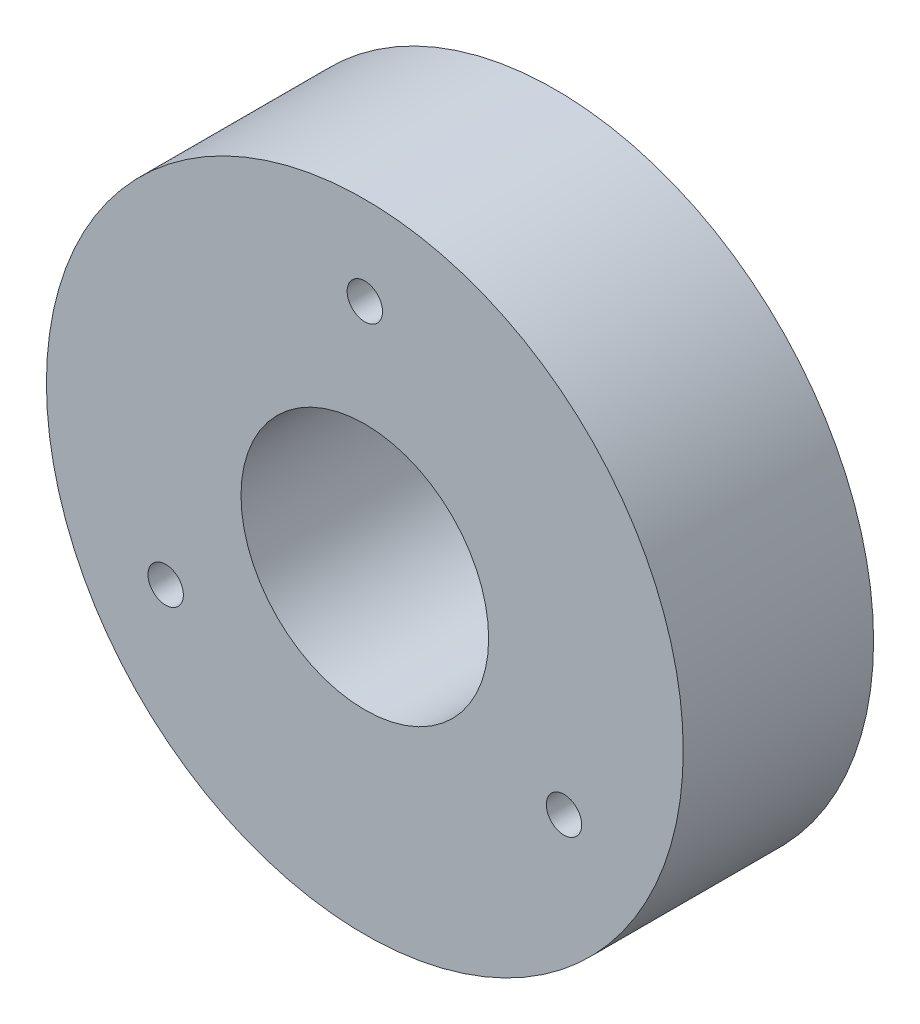
SolidWorks part; units mm, degrees
material "AISI 1020 Steel, Cold Rolled"
ref_plane "Front Plane" through (0, 0, 0) normal (0, 0, 1) x (1, 0, 0)
ref_plane "Top Plane" through (0, 0, 0) normal (0, 1, 0) x (1, 0, 0)
ref_plane "Right Plane" through (0, 0, 0) normal (1, 0, 0) x (0, 0, -1)
sketch "Sketch1" plane through (0, 0, 0) normal (0, 0, 1) x (1, 0, 0)
  line L0 (0, 45) -> (0, -45) construction
  line L1 (-45, 0) -> (45, 0) construction
  circle A0 centre (0, 0) radius 45
  circle A1 centre (0, 0) radius 17.5
  circle A2 centre (0, 0) radius 5
  circle A7 centre (0, 32.5) radius 2.5
  circle A8 centre (28.1458, -16.25) radius 2.5
  circle A9 centre (-28.1458, -16.25) radius 2.5
  circle A10 centre (0, 0) radius 32.5 construction
  point P18 (0, 0)
  point P25 (0, 0)
  dimension "D5" = 5
  dimension "D7" = 35
  dimension "D8" = 10
  dimension "D9" = 90
  dimension "D10" = 65
  dimension "D2" = 3
extrude "Boss-Extrude1" add sketch "Sketch1" along normal blind 26.9 contours A0 A9 A8 A7 A1 region at (-43.7272, 0, 0)
extrude "Boss-Extrude2" add sketch "Sketch1<3>" against normal blind 26.9 separate body contours A2 region at (0, 0, 0)
sketch "Sketch1<3>" plane through (0, 0, 0) normal (0, 0, 1) x (1, 0, 0) same geometry as "Sketch1"
extrude "Boss-Extrude3" add sketch "Sketch1<4>" against normal blind 3.2 contours A1 A2 region at (-17.005, 0, 0)
sketch "Sketch1<4>" plane through (0, 0, 0) normal (0, 0, 1) x (1, 0, 0) same geometry as "Sketch1"
